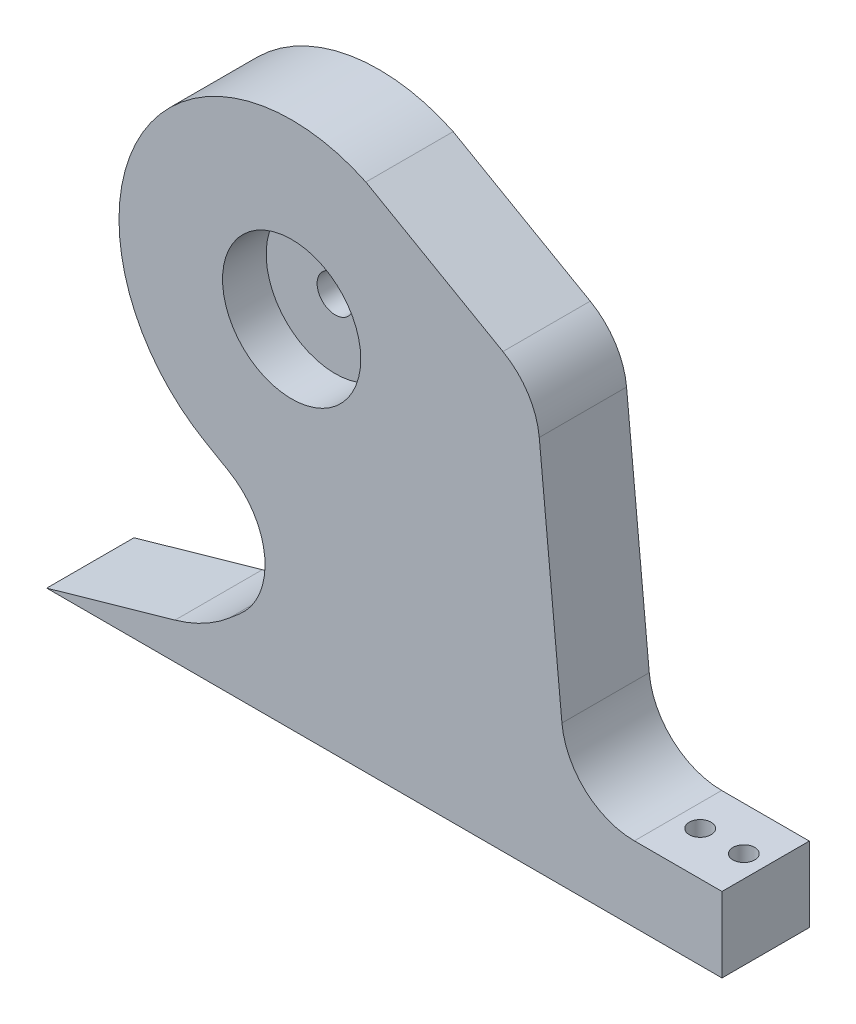
SolidWorks part; units mm, degrees
ref_plane "Front Plane" through (0, 0, 0) normal (0, 0, 1) x (1, 0, 0)
ref_plane "Top Plane" through (0, 0, 0) normal (0, 1, 0) x (1, 0, 0)
ref_plane "Right Plane" through (0, 0, 0) normal (1, 0, 0) x (0, 0, -1)
sketch "Sketch_body" plane through (0, 0, 0) normal (0, 0, 1) x (1, 0, 0)
  line L0 (21.2946, 15.4992) -> (22.7802, 0.0334)
  line L2 (-2.5397, 33.9855) -> (16.2995, 23.2268)
  line L3 (22.7802, 0.0334) -> (24.4112, -16.9452)
  line L4 (34.3653, -25.989) -> (46.4112, -25.989)
  line L5 (-24.6077, -7.9899) -> (-9.0967, -16.9452)
  line L7 (46.4112, -25.989) -> (46.4112, -36.2909)
  line L8 (46.4112, -36.2909) -> (24.4112, -36.2909)
  line L9 (24.4112, -36.2909) -> (-46.4112, -36.2909)
  line L10 (-9.0967, -16.9452) -> (-21.306, -27.2953)
  line L11 (-28.7712, -31.2775) -> (-46.4112, -36.2909)
  arc A0 (-24.6077, -7.9899) -> (-2.5397, 33.9855) centre (-12.7427, 12.5609) cw
  arc A1 (24.4112, -16.9452) -> (34.3653, -25.989) centre (34.3653, -15.989) ccw
  arc A2 (21.2946, 15.4992) -> (16.2995, 23.2268) centre (11.3404, 14.543) ccw
  arc A3 (-21.306, -27.2953) -> (-28.7712, -31.2775) centre (-34.2388, -12.0394) cw
  dimension "D1" = 10
  dimension "D2" = 10
  dimension "D3" = 22
  dimension "D4" = 10.3019
  dimension "D5" = 12.0458
extrude "body" add sketch "Sketch_body" along normal blind 12
sketch "Sketch_hole_bearing" plane through (0, 0, 12) normal (0, 0, 1) x (1, 0, 0)
  circle A2 centre (-12.7427, 12.5609) radius 9.5
  dimension "D1" = 19
extrude "hole bearing" cut sketch "Sketch_hole_bearing" against normal blind 6
sketch "Sketch3" plane through (0, 0, 6) normal (0, 0, 1) x (1, 0, 0)
  circle A0 centre (-12.7427, 12.5609) radius 2.5
extrude "Cut-Extrude6" cut sketch "Sketch3" against normal up to surface (6 mm away) up to face at (2.9745, -11.9508, 0)
sketch "Sketch4" plane through (0, -25.989, 0) normal (0, 1, 0) x (1, 0, 0)
  line L0 (46.4112, -12) -> (46.4112, 0) construction
  line L1 (46.4112, 0) -> (34.3653, 0) construction
  circle A0 centre (37.4112, -6) radius 1.5
  circle A1 centre (43.4112, -6) radius 1.5
  dimension "D1" = 3
  dimension "D2" = 3
  dimension "D3" = 3
  dimension "D4" = 6
  dimension "D5" = 6
extrude "Cut-Extrude7" cut sketch "Sketch4" against normal up to surface (10.3019 mm away) up to face at (0, -36.2909, 6)
fillet "Fillet2" radius 10 1 edges at (-9.0967, -16.9452, 6)
